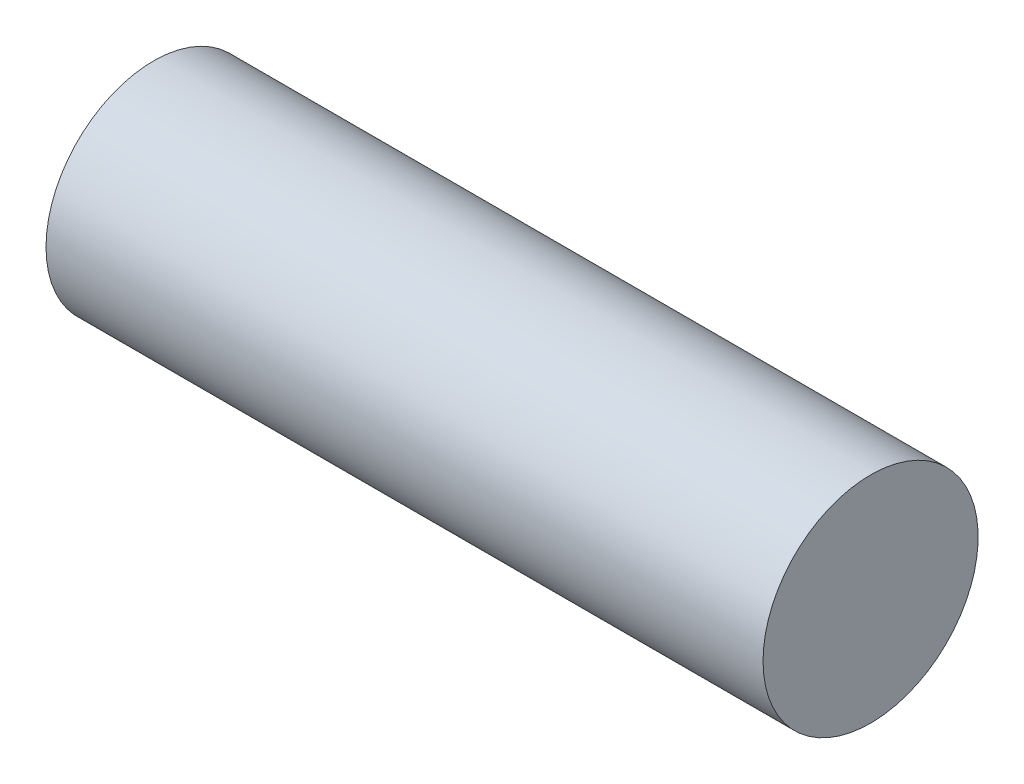
SolidWorks part; units mm, degrees
ref_plane "Front Plane" through (0, 0, 0) normal (0, 0, 1) x (1, 0, 0)
ref_plane "Top Plane" through (0, 0, 0) normal (0, 1, 0) x (1, 0, 0)
ref_plane "Right Plane" through (0, 0, 0) normal (1, 0, 0) x (0, 0, -1)
sketch "Pin_Inner Sketch" plane through (0, 0, 0) normal (0, 0, 1) x (1, 0, 0)
  line L0 (-1000, 0) -> (1000, 0) construction
  line L1 (70, 0) -> (70, 3)
  line L2 (70, 3) -> (90, 3)
  line L3 (90, 3) -> (90, 0)
  line L4 (90, 0) -> (70, 0)
revolve "Pin_Inner" add sketch "Pin_Inner Sketch" angle 360 about L0
ref_axis "Engine Axis" through (91, 0, 0) along (-1, 0, 0)
